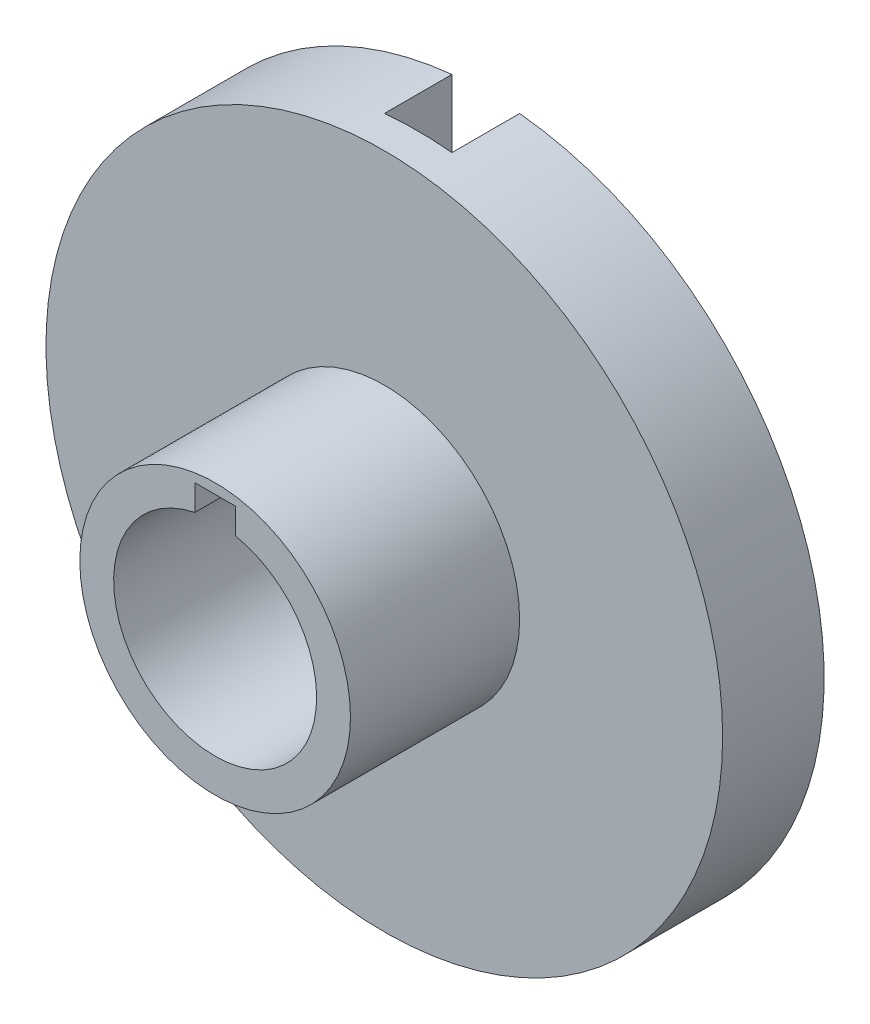
SolidWorks part; units mm, degrees
ref_plane "Front Plane" through (0, 0, 0) normal (0, 0, 1) x (1, 0, 0)
ref_plane "Top Plane" through (0, 0, 0) normal (0, 1, 0) x (1, 0, 0)
ref_plane "Right Plane" through (0, 0, 0) normal (1, 0, 0) x (0, 0, -1)
sketch "Sketch1" plane through (0, 0, 0) normal (0, 0, 1) x (1, 0, 0)
  circle A0 centre (0, 0) radius 50
  circle A1 centre (0, 0) radius 20
  circle A2 centre (0, 0) radius 15
  dimension "D1" = 100
  dimension "D2" = 40
  dimension "D3" = 30
extrude "Boss-Extrude1" add sketch "Sketch1" along normal blind 15 contours A0 A1 region at (-48.5858, 0, 0)
extrude "Boss-Extrude2" add sketch "Sketch1<3>" along normal blind 40 contours A1 A2 region at (-19.4343, 0, 0)
sketch "Sketch1<3>" plane through (0, 0, 0) normal (0, 0, 1) x (1, 0, 0) same geometry as "Sketch1"
sketch "Sketch2" plane through (0, 0, 0) normal (0, 0, 1) x (1, 0, 0)
  line L0 (0, 0) -> (0, 50000) construction
  line L1 (0, 0) -> (-50000, 0) construction
  line L3 (-3, 14.5) -> (3, 14.5)
  line L4 (-3, 14.5) -> (-3, 18.5)
  line L5 (-3, 18.5) -> (3, 18.5)
  line L6 (3, 14.5) -> (3, 18.5)
  point P10 (3, 16.5)
  dimension "D1" = 4
  dimension "D2" = 6
  dimension "D3" = 3
  dimension "D4" = 14.5
extrude "Cut-Extrude1" cut sketch "Sketch2" along normal blind 80
sketch "Sketch3" plane through (0, 0, 0) normal (0, 1, 0) x (1, 0, 0)
  line L0 (0, 0) -> (0, 50000) construction
  line L1 (50, 0) -> (-50, 0) construction
  line L2 (0, 0) -> (-50000, 0) construction
  line L4 (-5, -10) -> (5, -10)
  line L5 (-5, -10) -> (-5, 0)
  line L6 (-5, 0) -> (5, 0)
  line L7 (5, -10) -> (5, 0)
  point P4 (0, 0)
  dimension "D1" = 10
  dimension "D2" = 10
  dimension "D3" = 5
  dimension "D4" = 10
extrude "Cut-Extrude2" cut sketch "Sketch3" against normal blind 80 and the other way blind 80
